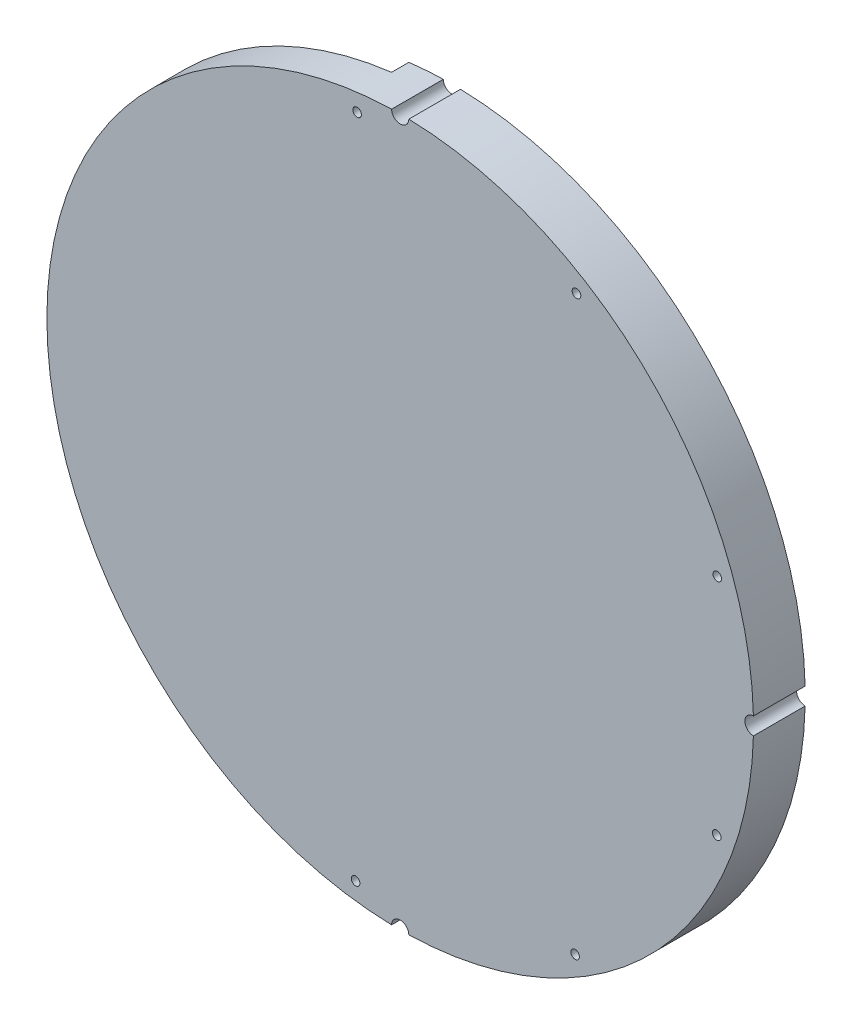
SolidWorks part; units mm, degrees
ref_plane "Front Plane" through (0, 0, 0) normal (0, 0, 1) x (1, 0, 0)
ref_plane "Top Plane" through (0, 0, 0) normal (0, 1, 0) x (1, 0, 0)
ref_plane "Right Plane" through (0, 0, 0) normal (1, 0, 0) x (0, 0, -1)
sketch "Sketch1" plane through (0, 0, 0) normal (0, 0, 1) x (1, 0, 0)
  circle A0 centre (0, 0) radius 82
  dimension "D1" = 164
extrude "Boss-Extrude1" add sketch "Sketch1" along normal blind 8
sketch "Sketch3" plane through (0, 0, 0) normal (0, 0, -1) x (-1, 0, 0)
  line L0 (10, 81.388) -> (10, 74.8348)
  line L1 (10, -74.8348) -> (10, -81.388)
  arc A0 (10, 74.8348) -> (10, -74.8348) centre (0, 0) ccw
  circle A1 centre (0, 0) radius 82 construction
  arc A2 (10, 81.388) -> (10, -81.388) centre (0, 0) ccw
  dimension "D1" = 151
  dimension "D2" = 10
extrude "Boss-Extrude3" add sketch "Sketch3" along normal blind 4
fillet "Fillet1" radius 10 2 edges at (-10, 74.8348, -2) (-10, -74.8348, -2)
sketch "Sketch2" plane through (0, 0, 8) normal (0, 0, 1) x (1, 0, 0)
  circle A0 centre (0, 60) radius 2
  dimension "D1" = 4
  dimension "D2" = 60
sketch "Sketch8" plane through (0, 0, -4) normal (0, 0, -1) x (-1, 0, 0)
  circle A2 centre (0, 82) radius 2
  arc A3 (10, 81.388) -> (10, -81.388) centre (0, 0) ccw construction
  dimension "D1" = 4
extrude "Cut-Extrude4" cut sketch "Sketch8" against normal blind 12
pattern_circular "CirPattern4" count 3 every 90 about axis through (0, 0, 0) along (0, 0, 1) of "Cut-Extrude4"
sketch "Sketch9" plane through (0, 0, 0) normal (0, 0, -1) x (-1, 0, 0)
  circle A0 centre (10, 77.3563) radius 1
  point P2 (0, 0)
  point P4 (0, 0)
  dimension "D1" = 2
  dimension "D2" = 10
  dimension "D3" = 78
extrude "Cut-Extrude5" cut sketch "Sketch9" against normal blind 12 and the other way blind 26 contours A0
pattern_circular "CirPattern5" count 6 every 39 about axis through (0, 0, 0) along (0, 0, 1) of "Cut-Extrude5"
